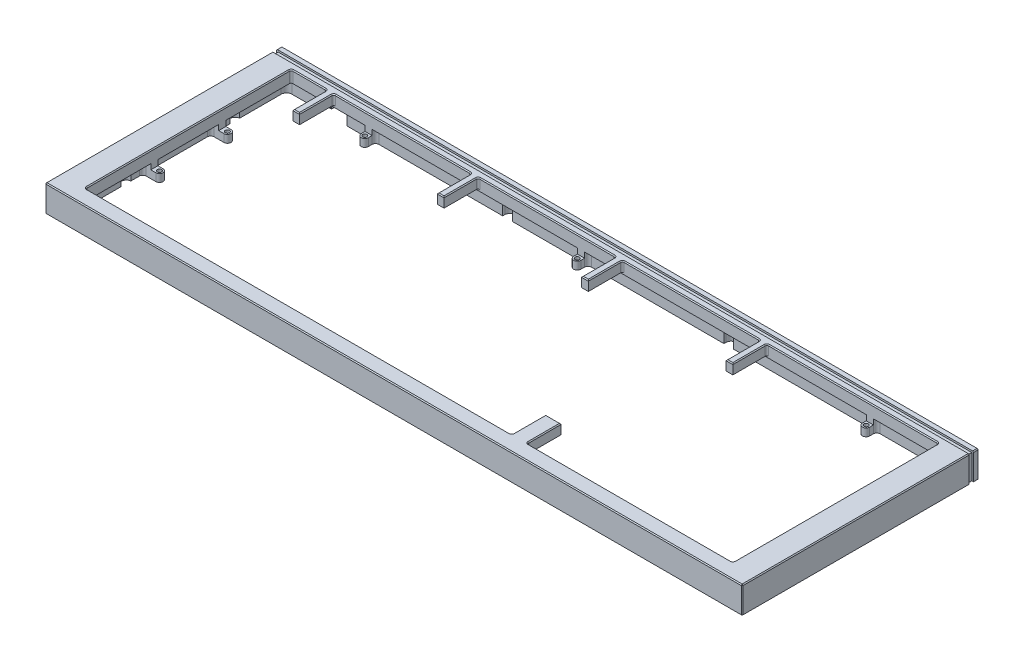
SolidWorks part; units mm, degrees
material "6061-T6 (SS)"
ref_plane "Front Plane" through (0, 0, 0) normal (0, 0, 1) x (1, 0, 0)
ref_plane "Top Plane" through (0, 0, 0) normal (0, 1, 0) x (1, 0, 0)
ref_plane "Right Plane" through (0, 0, 0) normal (1, 0, 0) x (0, 0, -1)
sketch "Sketch1" plane through (0, 0, 0) normal (0, 1, 0) x (1, 0, 0)
  line L1 (0, 0) -> (390.74, 0)
  line L2 (0, 0) -> (0, 132.7)
  line L3 (0, 132.7) -> (390.74, 132.7)
  line L4 (390.74, 0) -> (390.74, 132.7)
  line L5 (13.92, 124) -> (376.82, 124)
  line L6 (13.92, 124) -> (13.92, 8.7)
  line L7 (13.92, 8.7) -> (376.82, 8.7)
  line L8 (376.82, 124) -> (376.82, 8.7)
  point P9 (195.37, 124)
  point P10 (195.37, 132.7)
  point P11 (13.92, 66.35)
  point P12 (0, 66.35)
  dimension "D1" = 362.9
  dimension "D2" = 115.3
  dimension "D3" = 8.7
  dimension "D4" = 13.92
extrude "Main Body" add sketch "Sketch1" along normal blind 14.8
sketch "Sketch2" plane through (0, 0, 0) normal (0, -1, 0) x (1, 0, 0)
  line L0 (390.74, -132.7) -> (0, -132.7) construction
  line L1 (388.74, -130.7) -> (2, -130.7)
  line L2 (388.74, -130.7) -> (388.74, -2)
  line L3 (388.74, -2) -> (2, -2)
  line L4 (2, -130.7) -> (2, -2)
  line L5 (390.74, 0) -> (390.74, -132.7) construction
  point P4 (195.37, -130.7)
  point P7 (195.37, -132.7)
  point P8 (388.74, -66.35)
  point P11 (390.74, -66.35)
  dimension "D1" = 2
  dimension "D2" = 2
extrude "Alignment Guide" cut sketch "Sketch2" against normal blind 1 contours L2 L1 L4 L3
sketch "Sketch3" plane through (0, 14.8, 0) normal (0, 1, 0) x (1, 0, 0)
  line L0 (13.92, 8.7) -> (376.82, 8.7) construction
  line L1 (252.82, 27.8) -> (261.52, 27.8)
  line L2 (252.82, 27.8) -> (252.82, 8.7)
  line L3 (252.82, 8.7) -> (261.52, 8.7)
  line L4 (261.52, 27.8) -> (261.52, 8.7)
  line L5 (376.82, 8.7) -> (376.82, 124) construction
  line L6 (376.82, 124) -> (13.92, 124) construction
  line L7 (33.92, 124) -> (37.72, 124)
  line L8 (33.92, 124) -> (33.92, 104.9)
  line L9 (33.92, 104.9) -> (37.72, 104.9)
  line L10 (37.72, 124) -> (37.72, 104.9)
  line L11 (13.92, 124) -> (13.92, 8.7) construction
  line L12 (114.92, 124) -> (118.72, 124)
  line L13 (114.92, 124) -> (114.92, 104.9)
  line L14 (114.92, 104.9) -> (118.72, 104.9)
  line L15 (118.72, 124) -> (118.72, 104.9)
  line L16 (195.82, 124) -> (199.62, 124)
  line L17 (195.82, 124) -> (195.82, 104.9)
  line L18 (195.82, 104.9) -> (199.62, 104.9)
  line L19 (199.62, 124) -> (199.62, 104.9)
  line L20 (276.82, 124) -> (280.62, 124)
  line L21 (276.82, 124) -> (276.82, 104.9)
  line L22 (276.82, 104.9) -> (280.62, 104.9)
  line L23 (280.62, 124) -> (280.62, 104.9)
  point P8 (257.17, 8.7)
  dimension "D1" = 115.3
  dimension "D2" = 124
  dimension "D3" = 19.1
  dimension "D4" = 3.8
  dimension "D5" = 19.1
  dimension "D6" = 77.2
  dimension "D7" = 77.1
  dimension "D8" = 77.2
  dimension "D9" = 20
extrude "Blockers" add sketch "Sketch3" against normal blind 5.5
fillet "Fillet5" radius 1 14 edges at (280.62, 12.05, -124) (276.82, 12.05, -124) (195.82, 12.05, -124) (199.62, 12.05, -124) (118.72, 12.05, -124) (114.92, 12.05, -124) (33.92, 12.05, -124) (37.72, 12.05, -124) (13.92, 7.9, -124) (13.92, 7.9, -8.7) (252.82, 12.05, -8.7) (261.52, 12.05, -8.7) (376.82, 7.9, -8.7) (376.82, 7.9, -124)
sketch "Sketch4" plane through (0, 1, 0) normal (0, -1, 0) x (1, 0, 0)
  line L0 (0, 0) -> (390.74, 0) construction
  line L1 (381.27, -125.9) -> (9.47, -125.9)
  line L2 (381.27, -125.9) -> (381.27, -6.8)
  line L3 (381.27, -6.8) -> (9.47, -6.8)
  line L4 (9.47, -125.9) -> (9.47, -6.8)
  line L5 (390.74, 0) -> (390.74, -132.7) construction
  point P4 (195.37, -6.8)
  point P7 (195.37, 0)
  point P8 (381.27, -66.35)
  point P11 (390.74, -66.35)
  dimension "D1" = 119.1
  dimension "D2" = 371.8
extrude "PCB Cutout" cut sketch "Sketch4" against normal offset from surface (7.3 mm away) 6.5 up to face at (195.37, 14.8, -66.35)
fillet "Fillet4" radius 3 8 edges at (9.47, 4.65, -6.8) (9.47, 4.65, -125.9) (381.27, 4.65, -125.9) (381.27, 4.65, -6.8) (2, 0.5, -130.7) (2, 0.5, -2) (388.74, 0.5, -2) (388.74, 0.5, -130.7)
sketch "Sketch6" plane through (0, 1, 0) normal (0, -1, 0) x (1, 0, 0)
  line L0 (381.27, -9.8) -> (381.27, -122.9) construction
  line L1 (254.62, -127.1) -> (260.12, -127.1)
  line L2 (254.62, -127.1) -> (254.62, -125.9)
  line L3 (254.62, -125.9) -> (260.12, -125.9)
  line L4 (260.12, -127.1) -> (260.12, -125.9)
  line L5 (12.47, -125.9) -> (378.27, -125.9) construction
  line L11 (378.27, -6.8) -> (12.47, -6.8) construction
  line L16 (260.12, -6.8) -> (254.62, -6.8)
  line L17 (260.12, -6.8) -> (260.12, -4.8)
  line L18 (260.12, -4.8) -> (254.62, -4.8)
  line L19 (254.62, -6.8) -> (254.62, -4.8)
  line L21 (0, 0) -> (390.74, 0) construction
  line L24 (390.74, -66.35) -> (195.37, -66.35) construction
  line L25 (390.74, 0) -> (390.74, -132.7) construction
  line L26 (328.6755, -66.35) -> (328.6755, -130.7) construction
  line L27 (385.74, -130.7) -> (5, -130.7) construction
  line L28 (328.6755, -66.35) -> (328.6755, -8.7) construction
  line L29 (375.82, -8.7) -> (14.92, -8.7) construction
  line L55 (390.74, -132.7) -> (0, -132.7) construction
  line L56 (195.37, -132.7) -> (195.37, 0) construction
  line L57 (136.12, -6.8) -> (136.12, -4.8)
  line L58 (130.62, -4.8) -> (136.12, -4.8)
  line L59 (130.62, -6.8) -> (130.62, -4.8)
  line L60 (130.62, -6.8) -> (136.12, -6.8)
  line L61 (130.62, -127.1) -> (130.62, -125.9)
  line L62 (136.12, -125.9) -> (130.62, -125.9)
  line L63 (136.12, -127.1) -> (136.12, -125.9)
  line L64 (136.12, -127.1) -> (130.62, -127.1)
  circle A0 centre (381.07, -96.85) radius 2.75
  circle A1 centre (381.07, -35.85) radius 2.75
  circle A2 centre (257.37, -4.8) radius 2.75
  circle A3 centre (257.37, -127.1) radius 2.75
  circle A8 centre (133.37, -4.8) radius 2.75
  circle A9 centre (9.67, -35.85) radius 2.75
  circle A10 centre (9.67, -96.85) radius 2.75
  circle A11 centre (133.37, -127.1) radius 2.75
  point P25 (195.37, -66.35)
  point P32 (257.37, -125.9)
  point P33 (257.37, -6.8)
  line M17 (12.47, -6.8) -> (378.27, -6.8)
  line M18 (381.27, -9.8) -> (381.27, -122.9)
  line M19 (378.27, -125.9) -> (12.47, -125.9)
  line M20 (9.47, -122.9) -> (9.47, -9.8)
  dimension "D4" = 5.5
  dimension "D5" = 62
  dimension "D1" = 30.5
  dimension "D2" = 4.8
  dimension "D3" = 30.5
  dimension "D6" = 0.2
  dimension "D7" = 5.6
extrude "PlateTabs" cut sketch "Sketch6" against normal up to surface (7.3 mm away) contours A0 M18 | A1 M18 | A2 L19 M17 | L16 A2 L18 | A2 L17 M17 | L18 A2 | L1 A3 | L1 A3 L3 | A3 L2 M19 | A11 L64 | A11 L64 L62 | A10 M20 | A9 M20 | A8 L58 | A8 L60 L58 | A3 L4 M19 | A8 L59 M17 | L57 A8 M17 | A11 L63 M19 | L61 A11 M19 | A11 | L59 L58 L57 L60 | A3 region at (257.37, 1, -126.5102) region at (136.0381, 1, -126.1969) region at (257.37, 1, -128.2671) region at (254.7019, 1, -126.1969) region at (260.0381, 1, -126.1969) region at (133.37, 1, -126.5102) region at (133.37, 1, -128.2671) region at (130.7019, 1, -126.1969) region at (135.8701, 1, -6.317) region at (259.8701, 1, -6.317) region at (257.37, 1, -5.7445) region at (257.37, 1, -3.6329) region at (254.8699, 1, -6.317) region at (133.37, 1, -5.7445) region at (133.37, 1, -3.6329) region at (130.8699, 1, -6.317) region at (382.3459, 1, -96.85) region at (382.3459, 1, -35.85) region at (8.3941, 1, -96.85) region at (8.3941, 1, -35.85) up to face at (195.37, 8.3, -66.35)
sketch "Sketch9" plane through (0, 0, -132.7) normal (0, 0, -1) x (-1, 0, 0)
  line L1 (-41.8, 0) -> (-29.8, 0)
  line L2 (-41.8, 0) -> (-41.8, 3.2)
  line L3 (-41.8, 3.2) -> (-29.8, 3.2)
  line L4 (-29.8, 0) -> (-29.8, 3.2)
  line L5 (-390.74, 0) -> (0, 0) construction
  line L7 (0, 14.8) -> (0, 0) construction
  point P6 (-35.8, 3.2)
  dimension "D1" = 3.2
  dimension "D3" = 12
  dimension "D4" = 35.8
extrude "USB Cutout" cut sketch "Sketch9" against normal up to surface (8.7 mm away) up to face at (164.89, 11.95, -124)
sketch "Sketch11" plane through (0, 0, -125.9) normal (0, 0, 1) x (1, 0, 0)
  line L0 (130.62, 8.3) -> (12.47, 8.3) construction
  line L1 (43.3, 1) -> (28.3, 1)
  line L2 (43.3, 1) -> (43.3, 8.3)
  line L3 (43.3, 8.3) -> (28.3, 8.3)
  line L4 (28.3, 1) -> (28.3, 8.3)
  line L7 (12.47, 1) -> (29.8, 1) construction
  line L8 (29.8, 3.2) -> (41.8, 3.2) construction
  point P8 (35.8, 1)
  point P18 (35.8, 3.2)
  dimension "D1" = 15
extrude "PCB Clearance" cut sketch "Sketch11" against normal blind 3.9
fillet "Fillet7" radius 2.5 2 edges at (28.3, 4.65, -129.8) (43.3, 4.65, -129.8)
sketch "Sketch12" plane through (0, 8.3, 0) normal (0, -1, 0) x (1, 0, 0)
  line L0 (195.37, -132.7) -> (195.37, 0) construction
  line L2 (14.92, -124) -> (375.82, -124) construction
  line L3 (0, 0) -> (390.74, 0) construction
  line L5 (390.74, -132.7) -> (41.8, -132.7) construction
  line L8 (376.82, -123) -> (376.82, -9.7) construction
  arc A0 (381.27, -38.5927) -> (381.27, -33.1073) centre (381.07, -35.85) ccw construction
  arc A1 (381.27, -99.5927) -> (381.27, -94.1073) centre (381.07, -96.85) ccw construction
  point P0 (257.37, -127.1)
  point P1 (381.42, -96.85)
  point P2 (381.42, -35.85)
  point P3 (257.37, -4.85)
  point P7 (195.37, -66.35)
  point P8 (133.37, -4.85)
  point P10 (9.32, -35.85)
  point P14 (9.32, -96.85)
  point P16 (133.37, -127.1)
  point P34 (383.82, -35.85)
  point P39 (383.82, -96.85)
  dimension "D1" = 3.1
  dimension "D2" = 61.5
  dimension "D3" = 4.6
  dimension "D4" = 62
chamfer "Chamfer1" distance 0.5 46 edges at (14.2129, 14.8, -8.9929) (133.37, 14.8, -8.7) (252.5271, 14.8, -8.9929) (252.82, 14.8, -18.75) (257.17, 14.8, -27.8) (261.52, 14.8, -18.75) (261.8129, 14.8, -8.9929) (319.17, 14.8, -8.7) (376.5271, 14.8, -8.9929) (376.82, 14.8, -66.35) (376.5271, 14.8, -123.7071) (328.72, 14.8, -124) (280.9129, 14.8, -123.7071) (280.62, 14.8, -113.95) (278.72, 14.8, -104.9) (276.82, 14.8, -113.95) (276.5271, 14.8, -123.7071) (238.22, 14.8, -124) (199.9129, 14.8, -123.7071) (199.62, 14.8, -113.95) (197.72, 14.8, -104.9) (195.82, 14.8, -113.95) (195.5271, 14.8, -123.7071) (157.27, 14.8, -124) (119.0129, 14.8, -123.7071) (118.72, 14.8, -113.95) (116.82, 14.8, -104.9) (114.92, 14.8, -113.95) (114.6271, 14.8, -123.7071) (76.32, 14.8, -124) (38.0129, 14.8, -123.7071) (37.72, 14.8, -113.95) (35.82, 14.8, -104.9) (33.92, 14.8, -113.95) (33.6271, 14.8, -123.7071) (23.92, 14.8, -124) (14.2129, 14.8, -123.7071) (13.92, 14.8, -66.35) (195.37, 14.8, -132.7) (390.74, 14.8, -66.35) (195.37, 14.8, 0) (0, 14.8, -66.35) (390.74, 7.4, -132.7) (390.74, 7.4, 0) (0, 7.4, -132.7) (0, 7.4, 0)
chamfer "Chamfer2" distance 0.1 5 edges at (390.74, 0, -66.35) (195.37, 0, 0) (0, 0, -66.35) (15.15, 0, -132.7) (216.02, 0, -132.7)
sketch "Sketch27" plane through (0, 14.8, 0) normal (0, 1, 0) x (1, 0, 0)
  line L0 (0, 0.5) -> (0, 132.2) construction
  line L1 (0, 129.7) -> (390.74, 129.7)
  line L2 (0, 129.7) -> (0, 127.2)
  line L3 (0, 127.2) -> (390.74, 127.2)
  line L4 (390.74, 129.7) -> (390.74, 127.2)
  line L5 (390.74, 132.2) -> (390.74, 0.5) construction
  line L8 (0.5, 132.7) -> (390.24, 132.7) construction
  dimension "D1" = 2.5
  dimension "D2" = 3
extrude "Cut-Extrude11" cut sketch "Sketch27" against normal blind 1
sketch "Sketch28" plane through (0, 13.8, 0) normal (0, 1, 0) x (1, 0, 0)
  line L1 (0, 129.7) -> (1, 129.7)
  line L2 (0, 129.7) -> (0, 127.2)
  line L3 (0, 127.2) -> (1, 127.2)
  line L4 (1, 129.7) -> (1, 127.2)
  line L5 (389.74, 129.7) -> (390.74, 129.7)
  line L6 (389.74, 129.7) -> (389.74, 127.2)
  line L7 (389.74, 127.2) -> (390.74, 127.2)
  line L8 (390.74, 129.7) -> (390.74, 127.2)
  line L9 (390.74, 129.7) -> (0, 129.7) construction
  line L10 (0, 127.2) -> (390.74, 127.2) construction
  dimension "D1" = 1
  dimension "D2" = 1
extrude "Cut-Extrude12" cut sketch "Sketch28" against normal through all
sketch "Sketch21" [suppressed] plane through (0, 14.8, 0) normal (0, 1, 0) x (1, 0, 0)
  line L0 (0.5, 132.7) -> (390.24, 132.7) construction
  line L1 (382.53, 132.7) -> (385.03, 132.7)
  line L2 (382.53, 132.7) -> (382.53, 72.7)
  line L3 (382.53, 72.7) -> (385.03, 72.7)
  line L4 (385.03, 132.7) -> (385.03, 72.7)
  line L5 (390.74, 132.2) -> (390.74, 129.7) construction
  line L6 (390.74, 129.1) -> (294.74, 129.1)
  line L7 (390.74, 129.1) -> (390.74, 127.6)
  line L8 (390.74, 127.6) -> (294.74, 127.6)
  line L9 (294.74, 129.1) -> (294.74, 127.6)
  line L10 (362.9081, 132.2) -> (362.9081, 124.5) construction
  line L11 (390.24, 132.2) -> (0.5, 132.2) construction
  line L12 (281.62, 124.5) -> (375.82, 124.5) construction
  line L13 (365.5702, 129.1) -> (365.5702, 127.6) construction
  line L14 (377.32, 119.5259) -> (390.24, 119.5259) construction
  line L15 (377.32, 123) -> (377.32, 9.7) construction
  line L16 (390.24, 0.5) -> (390.24, 127.2) construction
  line L17 (382.53, 116.0504) -> (385.03, 116.0504) construction
  point P28 (383.78, 116.0504)
  point P29 (383.78, 119.5259)
  point P30 (365.5702, 128.35)
  point P31 (362.9081, 128.35)
  dimension "D1" = 2.5
  dimension "D2" = 1.5
  dimension "D3" = 60
  dimension "D4" = 96
extrude "Cut-Extrude5" [suppressed] cut sketch "Sketch21" against normal blind 1 contours L4 L3 L2 L1 | L8 L9 L6 L7
sketch "Sketch23" [suppressed] plane through (390.74, 0, 0) normal (1, 0, 0) x (0, 0, -1)
  line L0 (129.1, 13.8) -> (129.1, 14.3) construction
  line L1 (127.6, 13.8) -> (129.1, 13.8)
  line L2 (127.6, 13.8) -> (127.6, 0)
  line L3 (127.6, 0) -> (129.1, 0)
  line L4 (129.1, 13.8) -> (129.1, 0)
extrude "Cut-Extrude6" [suppressed] cut sketch "Sketch23" against normal blind 1
sketch "Sketch19" plane through (0, 14.8, 0) normal (0, 1, 0) x (1, 0, 0)
  line L0 (0.5, 132.7) -> (390.24, 132.7) construction
  line L1 (5.46, 132.7) -> (8.46, 132.7)
  line L2 (5.46, 132.7) -> (5.46, 0)
  line L3 (5.46, 0) -> (8.46, 0)
  line L4 (8.46, 132.7) -> (8.46, 0)
  line L7 (382.28, 132.7) -> (385.28, 132.7)
  line L8 (382.28, 132.7) -> (382.28, 0)
  line L9 (382.28, 0) -> (385.28, 0)
  line L10 (385.28, 132.7) -> (385.28, 0)
  line L11 (390.24, 0) -> (0.5, 0) construction
  line L12 (377.32, 110.209) -> (390.24, 110.209) construction
  line L13 (377.32, 123) -> (377.32, 9.7) construction
  line L14 (390.24, 0.5) -> (390.24, 127.2) construction
  line L15 (382.28, 106.8719) -> (385.28, 106.8719) construction
  line L16 (0.5, 106.8719) -> (13.42, 106.8719) construction
  line L17 (0.5, 132.2) -> (0.5, 129.7) construction
  line L18 (13.42, 9.7) -> (13.42, 123) construction
  line L19 (5.46, 102.7297) -> (8.46, 102.7297) construction
  point P12 (383.78, 106.8719)
  point P14 (383.78, 110.209)
  point P30 (6.96, 102.7297)
  point P31 (6.96, 106.8719)
  dimension "D1" = 3
  dimension "D2" = 3
extrude "Cut-Extrude3" [suppressed] cut sketch "Sketch19" against normal blind 1
sketch "Sketch17" plane through (0, 14.8, 0) normal (0, 1, 0) x (1, 0, 0)
  line L0 (390.24, 0.5) -> (390.24, 127.2) construction
  line L1 (5.71, 129.6) -> (385.03, 129.6)
  line L2 (5.71, 129.6) -> (5.71, -1.9)
  line L3 (5.71, -1.9) -> (385.03, -1.9)
  line L4 (385.03, 129.6) -> (385.03, -1.9)
  line L5 (8.21, 127.1) -> (382.53, 127.1)
  line L6 (8.21, 127.1) -> (8.21, 0.6)
  line L7 (8.21, 0.6) -> (382.53, 0.6)
  line L8 (382.53, 127.1) -> (382.53, 0.6)
  line L9 (390.24, 132.2) -> (0.5, 132.2) construction
  line L10 (21.2533, 132.2) -> (21.2533, 124.5) construction
  line L11 (14.92, 124.5) -> (32.92, 124.5) construction
  line L12 (25.2757, 129.6) -> (25.2757, 127.1) construction
  line L13 (0.5, 116.1326) -> (13.42, 116.1326) construction
  line L14 (0.5, 132.2) -> (0.5, 129.7) construction
  line L15 (13.42, 9.7) -> (13.42, 123) construction
  line L16 (5.71, 120.1548) -> (8.21, 120.1548) construction
  point P8 (382.53, 63.85)
  point P9 (385.03, 63.85)
  point P12 (390.24, 63.85)
  point P13 (195.37, 129.6)
  point P14 (195.37, 127.1)
  point P17 (195.37, 132.2)
  point P24 (25.2757, 128.35)
  point P25 (21.2533, 128.35)
  point P34 (6.96, 116.1326)
  point P35 (6.96, 120.1548)
  dimension "D1" = 2.5
  dimension "D2" = 2.5
extrude "Cut-Extrude1" [suppressed] cut sketch "Sketch17" against normal blind 1
hole_wizard "M2x0.4 Tapped Hole1" positions "3DSketch3" profile "Sketch31" tap size "M2x0.4" standard "ANSI Metric"
sketch3d "3DSketch3"
  point P0 (381.42, 8.3, -96.85)
  point P3 (381.42, 8.3, -35.85)
  point P7 (257.37, 8.3, -4.85)
  point P10 (133.37, 8.3, -4.85)
  point P13 (9.32, 8.3, -35.85)
  point P16 (9.32, 8.3, -96.85)
  point P19 (133.37, 8.3, -127.1)
  point P22 (257.37, 8.3, -127.1)
sketch "Sketch31" plane through (381.42, 8.3, -96.85) normal (1, 0, 0) x (0, 0, -1)
  line L0 (0, 0) -> (0, 4.4807)
  line L1 (0, 4.4807) -> (0.8, 4)
  line L2 (0.8, 4) -> (0.8, 0)
  line L5 (0.8, 0) -> (0, 0)
  line L10 (0, 4.4807) -> (-0.8, 4) construction
  line L11 (0, -6.35) -> (0, 107.95) construction
  dimension "Tap Drill Dia." = 1.6
  dimension "Tap Drill Depth" = 4
  dimension "Drill Angle" = 118
cosmetic thread "Hole Thread19" parameters "D1"=4, "D2"=2
cosmetic thread "Hole Thread20" parameters "D1"=4, "D2"=2
cosmetic thread "Hole Thread21" parameters "D1"=4, "D2"=2
cosmetic thread "Hole Thread22" parameters "D1"=4, "D2"=2
cosmetic thread "Hole Thread23" parameters "D1"=4, "D2"=2
cosmetic thread "Hole Thread24" parameters "D1"=4, "D2"=2
cosmetic thread "Hole Thread25" parameters "D1"=4, "D2"=2
cosmetic thread "Hole Thread26" parameters "D1"=4, "D2"=2
fillet "Fillet8" radius 0.1 9 edges at (213.77, 0, -130.7) (387.8613, 0, -129.8213) (17.4, 0, -130.7) (2.8787, 0, -129.8213) (2, 0, -66.35) (2.8787, 0, -2.8787) (195.37, 0, -2) (387.8613, 0, -2.8787) (388.74, 0, -66.35)
sketch "Sketch32" plane through (0, 1, 0) normal (0, -1, 0) x (1, 0, 0)
  line L1 (0, -127.2) -> (0, -0.5) construction
  line L3 (378.27, -125.9) -> (260.12, -125.9) construction
  line L4 (340.3, -121.9) -> (336.3, -121.9)
  line L5 (340.3, -121.9) -> (340.3, -125.9)
  line L6 (340.3, -125.9) -> (336.3, -125.9)
  line L7 (336.3, -121.9) -> (336.3, -125.9)
  line L8 (254.62, -125.9) -> (136.12, -125.9) construction
  line L9 (178.4, -121.9) -> (174.4, -121.9)
  line L10 (178.4, -121.9) -> (178.4, -125.9)
  line L11 (178.4, -125.9) -> (174.4, -125.9)
  line L12 (174.4, -121.9) -> (174.4, -125.9)
  line L13 (43.3, -125.9) -> (130.62, -125.9) construction
  line L14 (59.3, -121.9) -> (55.3, -121.9)
  line L15 (59.3, -121.9) -> (59.3, -125.9)
  line L16 (59.3, -125.9) -> (55.3, -125.9)
  line L17 (55.3, -121.9) -> (55.3, -125.9)
  line L18 (9.47, -38.5927) -> (9.47, -94.1073) construction
  line L19 (16.8, -83.4) -> (9.47, -83.4)
  line L20 (16.8, -83.4) -> (16.8, -87.4)
  line L21 (16.8, -87.4) -> (9.47, -87.4)
  line L22 (9.47, -83.4) -> (9.47, -87.4)
  line L23 (12.47, -6.8) -> (130.62, -6.8) construction
  line L24 (16.8, -45.3) -> (9.47, -45.3)
  line L25 (16.8, -45.3) -> (16.8, -49.3)
  line L26 (16.8, -49.3) -> (9.47, -49.3)
  line L27 (9.47, -45.3) -> (9.47, -49.3)
  line L28 (87.9, -11.6) -> (83.9, -11.6)
  line L29 (87.9, -11.6) -> (87.9, -6.8)
  line L30 (87.9, -6.8) -> (83.9, -6.8)
  line L31 (83.9, -11.6) -> (83.9, -6.8)
  line L32 (254.62, -6.8) -> (136.12, -6.8) construction
  line L33 (158.5, -11.6) -> (154.5, -11.6)
  line L34 (158.5, -11.6) -> (158.5, -6.8)
  line L35 (158.5, -6.8) -> (154.5, -6.8)
  line L36 (154.5, -11.6) -> (154.5, -6.8)
  line L37 (378.27, -6.8) -> (260.12, -6.8) construction
  line L38 (302.2, -11.6) -> (298.2, -11.6)
  line L39 (302.2, -11.6) -> (302.2, -6.8)
  line L40 (302.2, -6.8) -> (298.2, -6.8)
  line L41 (298.2, -11.6) -> (298.2, -6.8)
  line L42 (195.37, 0) -> (195.37, -132.6) construction
  line L43 (0.5, 0) -> (390.24, 0) construction
  line L44 (381.27, -45.3) -> (381.27, -49.3)
  line L45 (373.94, -49.3) -> (381.27, -49.3)
  line L46 (373.94, -45.3) -> (373.94, -49.3)
  line L47 (373.94, -45.3) -> (381.27, -45.3)
  line L48 (381.27, -83.4) -> (381.27, -87.4)
  line L49 (373.94, -87.4) -> (381.27, -87.4)
  line L50 (373.94, -83.4) -> (373.94, -87.4)
  line L51 (373.94, -83.4) -> (381.27, -83.4)
  line L52 (41.8, -132.6) -> (390.34, -132.6) construction
  line L53 (29.8, -132.7) -> (41.8, -132.7) construction
  circle A0 centre (338.3, -121.9) radius 2
  circle A1 centre (176.4, -121.9) radius 2
  circle A2 centre (57.3, -121.9) radius 2
  circle A3 centre (16.8, -85.4) radius 2
  circle A4 centre (16.8, -47.3) radius 2
  circle A5 centre (85.9, -11.6) radius 2
  circle A6 centre (156.5, -11.6) radius 2
  circle A7 centre (300.2, -11.6) radius 2
  circle A8 centre (373.94, -47.3) radius 2
  circle A9 centre (373.94, -85.4) radius 2
  point P82 (0, 0)
  point P83 (0, 0)
  point P84 (0, 0)
  dimension "D1" = 4
  dimension "D2" = 10.8
  dimension "D3" = 57.3
  dimension "D4" = 119.1
  dimension "D5" = 161.9
  dimension "D6" = 36.5
  dimension "D7" = 38.1
  dimension "D8" = 28.6
  dimension "D9" = 70.6
  dimension "D10" = 143.7
  dimension "D11" = 40.5
  dimension "D12" = 110.3
extrude "Boss-Extrude1" add sketch "Sketch32" against normal offset from surface (4.3 mm away) 3 contours A1 | L12 L11 L10 L9 | A0 | L5 L6 L7 L4 | A9 | L51 L48 L49 L50 | L47 L44 L45 L46 | A8 | L41 L40 L39 L38 | A7 | A6 | L36 L35 L34 L33 | A5 | L31 L30 L29 L28 | A4 | L26 L27 L24 L25 | A3 | L19 L22 L21 L20 | A2 | L15 L16 L17 L14 up to face at (381.42, 8.3, -97.65)
sketch "Sketch33" plane through (0, 8.3, 0) normal (0, -1, 0) x (1, 0, 0)
  line L0 (373.94, -83.4) -> (381.27, -83.4) construction
  line L1 (381.27, -87.4) -> (376.82, -87.4)
  line L2 (381.27, -87.4) -> (381.27, -83.4)
  line L3 (381.27, -83.4) -> (376.82, -83.4)
  line L4 (376.82, -87.4) -> (376.82, -83.4)
  line L5 (376.82, -123) -> (376.82, -9.7) construction
  line L6 (373.94, -45.3) -> (381.27, -45.3) construction
  line L7 (381.27, -49.3) -> (376.82, -49.3)
  line L8 (381.27, -49.3) -> (381.27, -45.3)
  line L9 (381.27, -45.3) -> (376.82, -45.3)
  line L10 (376.82, -49.3) -> (376.82, -45.3)
  line L11 (375.82, -8.7) -> (14.92, -8.7) construction
  line L12 (302.2, -6.8) -> (298.2, -6.8)
  line L13 (302.2, -6.8) -> (302.2, -8.7)
  line L14 (302.2, -8.7) -> (298.2, -8.7)
  line L15 (298.2, -6.8) -> (298.2, -8.7)
  line L16 (298.2, -11.6) -> (298.2, -6.8) construction
  line L17 (154.5, -11.6) -> (154.5, -6.8) construction
  line L18 (158.5, -6.8) -> (154.5, -6.8)
  line L19 (158.5, -6.8) -> (158.5, -8.7)
  line L20 (158.5, -8.7) -> (154.5, -8.7)
  line L21 (154.5, -6.8) -> (154.5, -8.7)
  line L22 (83.9, -11.6) -> (83.9, -6.8) construction
  line L23 (87.9, -6.8) -> (83.9, -6.8)
  line L24 (87.9, -6.8) -> (87.9, -8.7)
  line L25 (87.9, -8.7) -> (83.9, -8.7)
  line L26 (83.9, -6.8) -> (83.9, -8.7)
  line L27 (16.8, -49.3) -> (9.47, -49.3) construction
  line L28 (9.47, -45.3) -> (13.92, -45.3)
  line L29 (9.47, -45.3) -> (9.47, -49.3)
  line L30 (9.47, -49.3) -> (13.92, -49.3)
  line L31 (13.92, -45.3) -> (13.92, -49.3)
  line L32 (13.92, -9.7) -> (13.92, -123) construction
  line L33 (16.8, -87.4) -> (9.47, -87.4) construction
  line L34 (9.47, -83.4) -> (13.92, -83.4)
  line L35 (9.47, -83.4) -> (9.47, -87.4)
  line L36 (9.47, -87.4) -> (13.92, -87.4)
  line L37 (13.92, -83.4) -> (13.92, -87.4)
  line L38 (59.3, -121.9) -> (59.3, -125.9) construction
  line L39 (55.3, -125.9) -> (59.3, -125.9)
  line L40 (55.3, -125.9) -> (55.3, -124)
  line L41 (55.3, -124) -> (59.3, -124)
  line L42 (59.3, -125.9) -> (59.3, -124)
  line L43 (14.92, -124) -> (375.82, -124) construction
  line L44 (178.4, -121.9) -> (178.4, -125.9) construction
  line L45 (174.4, -125.9) -> (178.4, -125.9)
  line L46 (174.4, -125.9) -> (174.4, -124)
  line L47 (174.4, -124) -> (178.4, -124)
  line L48 (178.4, -125.9) -> (178.4, -124)
  line L49 (340.3, -121.9) -> (340.3, -125.9) construction
  line L50 (336.3, -125.9) -> (340.3, -125.9)
  line L51 (336.3, -125.9) -> (336.3, -124)
  line L52 (336.3, -124) -> (340.3, -124)
  line L53 (340.3, -125.9) -> (340.3, -124)
extrude "Boss-Extrude2" add sketch "Sketch33" along normal up to surface (3 mm away) up to face at (338.3, 5.3, -123.4)
fillet "Fillet9" radius 1.9 19 edges at (340.3, 4.65, -125.9) (336.3, 4.65, -125.9) (174.4, 4.65, -125.9) (178.4, 4.65, -125.9) (59.3, 4.65, -125.9) (55.3, 4.65, -125.9) (9.47, 4.65, -87.4) (9.47, 4.65, -83.4) (9.47, 4.65, -45.3) (9.47, 4.65, -49.3) (87.9, 4.65, -6.8) (83.9, 4.65, -6.8) (154.5, 4.65, -6.8) (158.5, 4.65, -6.8) (302.2, 4.65, -6.8) (298.2, 4.65, -6.8) (381.27, 4.65, -45.3) (381.27, 4.65, -49.3) (381.27, 4.65, -87.4)
sketch "Sketch34" plane through (0, 5.3, 0) normal (0, 1, 0) x (1, 0, 0)
  point P0 (16.8, 47.3)
  point P1 (16.8, 85.4)
  point P3 (85.9, 11.6)
  point P5 (156.5, 11.6)
  point P7 (300.2, 11.6)
  point P9 (373.94, 47.3)
  point P11 (373.94, 85.4)
  point P13 (338.3, 121.9)
  point P15 (176.4, 121.9)
  point P17 (57.3, 121.9)
hole_wizard "M2 Clearance Hole1" positions "3DSketch4" profile "Sketch35" hole size "M2" standard "ANSI Metric" end condition through all
sketch3d "3DSketch4"
  point P0 (57.3, 5.3, -121.9)
  point P3 (16.8, 5.3, -85.4)
  point P6 (16.8, 5.3, -47.3)
  point P9 (85.9, 5.3, -11.6)
  point P12 (156.5, 5.3, -11.6)
  point P15 (300.2, 5.3, -11.6)
  point P18 (373.94, 5.3, -47.3)
  point P21 (373.94, 5.3, -85.4)
  point P24 (338.3, 5.3, -121.9)
  point P27 (176.4, 5.3, -121.9)
sketch "Sketch35" plane through (57.3, 5.3, -121.9) normal (1, 0, 0) x (0, 0, 1)
  line L0 (0, 0) -> (0, 5.3)
  line L1 (0, 5.3) -> (1.2, 5.3)
  line L2 (1.2, 5.3) -> (1.2, 0)
  line L5 (1.2, 0) -> (0, 0)
  line L11 (0, -6.35) -> (0, 107.95) construction
  dimension "Thru Hole Dia." = 2.4
  dimension "Thru Hole Depth" = 5.3
